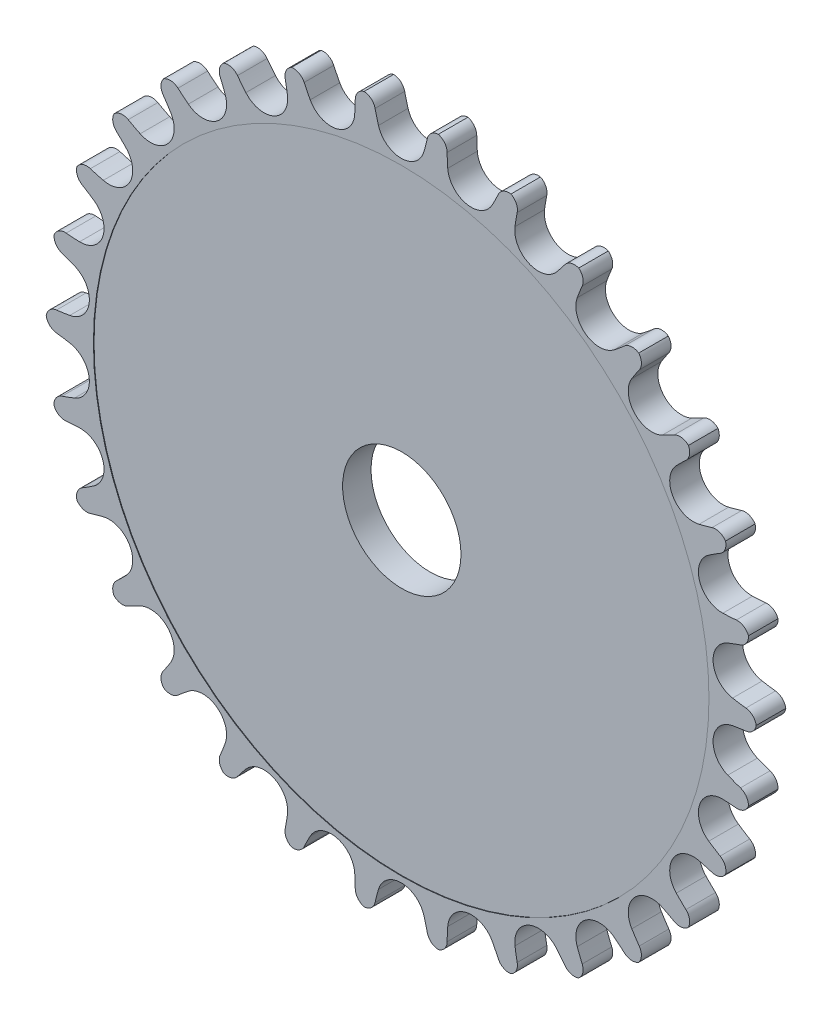
SolidWorks part; units mm, degrees
other "标注1"
sketch "草图4" plane through (-65.8763, -66, 10) normal (0, 0, 1) x (0, -1, 0)
ref_plane "前视基准面" through (0, 0, 0) normal (0, 0, 1) x (1, 0, 0)
ref_plane "上视基准面" through (0, 0, 0) normal (0, 1, 0) x (1, 0, 0)
ref_plane "右视基准面" through (0, 0, 0) normal (1, 0, 0) x (0, 0, -1)
sketch "草图1" plane through (0, 0, 0) normal (0, 0, 1) x (1, 0, 0)
  circle A0 centre (0, 0) radius 60
  dimension "D1" = 120
extrude "凸台-拉伸1" add sketch "草图1" along normal blind 5
sketch "草图2" plane through (0, 0, 5) normal (0, 0, 1) x (1, 0, 0)
  circle A0 centre (0, 0) radius 10
extrude "切除-拉伸1" cut sketch "草图2" against normal through all and the other way through all
sketch "草图5" plane through (0, 0, 0) normal (0, 0, -1) x (-1, 0, 0)
  line L0 (0, 66.4855) -> (0, -71.4103) construction
  arc A0 (-3.8429, 55.8901) -> (3.8429, 55.8901) centre (0, 57) ccw
  arc A1 (-4.7642, 59.8106) -> (-3.8429, 55.8901) centre (34.5863, 66.9892) ccw
  circle A2 centre (0, 0) radius 60 construction
  arc A3 (4.7642, 59.8106) -> (3.8429, 55.8901) centre (-34.5863, 66.9892) cw
  arc A4 (4.7642, 59.8106) -> (-4.7642, 59.8106) centre (0, 0) ccw
  dimension "D1" = 40
  dimension "D2" = 57
  dimension "D3" = 4
extrude "切除-拉伸2" cut sketch "草图5" against normal blind 10
pattern_circular "阵列(圆周)2" count 30 over 360 about axis through (0, 0, 0) along (0, 0, 1) of "切除-拉伸2"
fillet "圆角1" radius 2 60 edges at (7.7752, 59.4941, 2.5) (17.0954, 57.513, 2.5) (19.9748, 56.5774, 2.5) (28.6795, 52.7019, 2.5) (31.3014, 51.1881, 2.5) (39.0101, 45.5874, 2.5) (41.26, 43.5616, 2.5) (47.6358, 36.4806, 2.5) (49.4154, 34.0312, 2.5) (54.1796, 25.7793, 2.5) (55.411, 23.0135, 2.5) (58.3554, 13.9514, 2.5) (58.9849, 10.99, 2.5) (59.9809, 1.5138, 2.5) (59.9809, -1.5138, 2.5) (58.9849, -10.99, 2.5) (58.3554, -13.9514, 2.5) (55.411, -23.0135, 2.5) (54.1796, -25.7793, 2.5) (49.4154, -34.0312, 2.5) (47.6358, -36.4806, 2.5) (41.26, -43.5616, 2.5) (39.0101, -45.5874, 2.5) (31.3014, -51.1881, 2.5) (28.6795, -52.7019, 2.5) (19.9748, -56.5774, 2.5) (17.0954, -57.513, 2.5) (7.7752, -59.4941, 2.5) (4.7642, -59.8106, 2.5) (-4.7642, -59.8106, 2.5) (-7.7752, -59.4941, 2.5) (-17.0954, -57.513, 2.5) (-19.9748, -56.5774, 2.5) (-28.6795, -52.7019, 2.5) (-31.3014, -51.1881, 2.5) (-39.0101, -45.5874, 2.5) (-41.26, -43.5616, 2.5) (-47.6358, -36.4806, 2.5) (-49.4154, -34.0312, 2.5) (-54.1796, -25.7793, 2.5) (-55.411, -23.0135, 2.5) (-58.3554, -13.9514, 2.5) (-58.9849, -10.99, 2.5) (-59.9809, -1.5138, 2.5) (-59.9809, 1.5138, 2.5) (-58.9849, 10.99, 2.5) (-58.3554, 13.9514, 2.5) (-55.411, 23.0135, 2.5) (-54.1796, 25.7793, 2.5) (-49.4154, 34.0312, 2.5) (-47.6358, 36.4806, 2.5) (-41.26, 43.5616, 2.5) (-39.0101, 45.5874, 2.5) (-31.3014, 51.1881, 2.5) (-28.6795, 52.7019, 2.5) (-19.9748, 56.5774, 2.5) (-17.0954, 57.513, 2.5) (-7.7752, 59.4941, 2.5) (-4.7642, 59.8106, 2.5) (4.7642, 59.8106, 2.5)
sketch "草图6" plane through (0, 0, 0) normal (0, 0, -1) x (-1, 0, 0)
  circle A0 centre (0, 0) radius 52
extrude "切除-拉伸3" cut sketch "草图6" against normal blind 0.1
sketch "草图7" plane through (0, 0, 5) normal (0, 0, 1) x (1, 0, 0)
  circle A0 centre (0, 0) radius 52
extrude "切除-拉伸5" cut sketch "草图7" against normal blind 0.1
